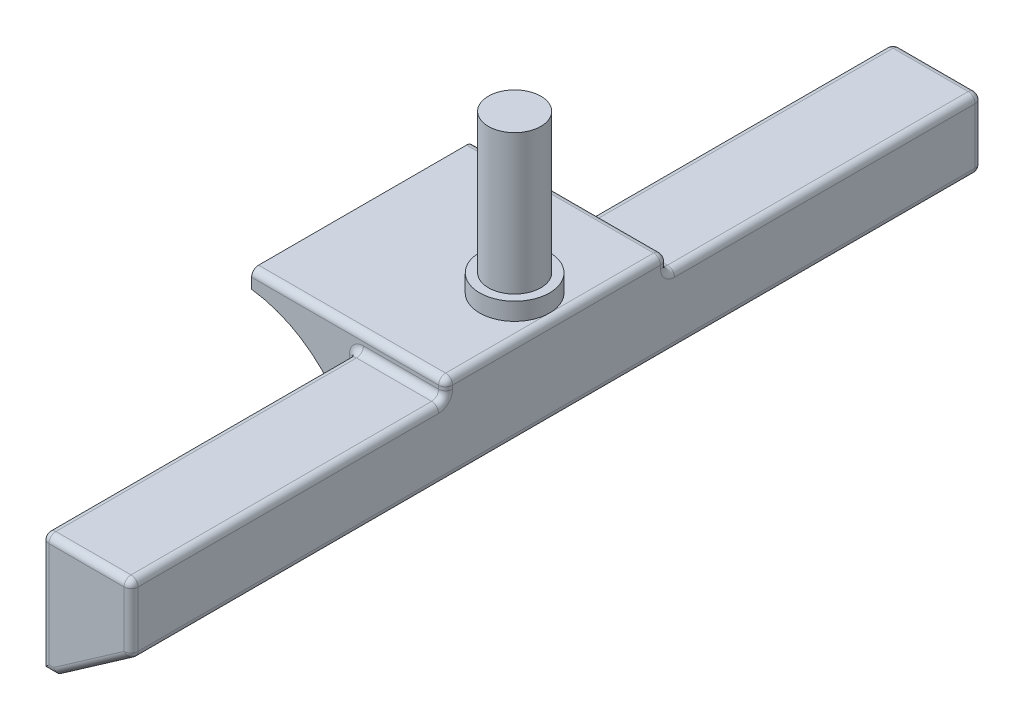
SolidWorks part; units mm, degrees
ref_plane "Front Plane" through (0, 0, 0) normal (0, 0, 1) x (1, 0, 0)
ref_plane "Top Plane" through (0, 0, 0) normal (0, 1, 0) x (1, 0, 0)
ref_plane "Right Plane" through (0, 0, 0) normal (1, 0, 0) x (0, 0, -1)
sketch "Sketch1" plane through (0, 0, 0) normal (0, 1, 0) x (1, 0, 0)
  line L0 (-4, 4) -> (-4, -239.5)
  line L1 (0, 0) -> (17.5, 0)
  line L2 (0, 0) -> (0, -235.5)
  line L3 (0, -235.5) -> (17.5, -235.5)
  line L4 (17.5, 0) -> (17.5, -235.5)
  line L5 (-4, -239.5) -> (21.5, -239.5)
  line L6 (21.5, 4) -> (21.5, -239.5)
  line L7 (-4, 4) -> (21.5, 4)
  dimension "D1" = 17.5
  dimension "D2" = 235.5
  dimension "D3" = 4
extrude "motor -panel connector " add sketch "Sketch1" along normal blind 34
sketch "Sketch3" plane through (0, 34, 0) normal (0, 1, 0) x (1, 0, 0)
  line L1 (-4, 4) -> (21.5, 4)
  line L2 (-4, 4) -> (-4, -239.5)
  line L3 (-4, -239.5) -> (21.5, -239.5)
  line L4 (21.5, 4) -> (21.5, -239.5)
extrude "motor-panel connecctor base" add sketch "Sketch3" against normal blind 4
sketch "Sketch4" plane through (0, 0, 239.5) normal (0, 0, 1) x (1, 0, 0)
  line L0 (0, 0) -> (21.5, 15)
  line L1 (21.5, 34) -> (21.5, 0) construction
  line L2 (21.5, 15) -> (21.5, 0)
  line L3 (21.5, 0) -> (0, 0)
  dimension "D1" = 19
extrude "up down connect cut" cut sketch "Sketch4" against normal blind 250
sketch "Sketch5" plane through (-4, 0, 0) normal (-1, 0, 0) x (0, 0, 1)
  line L0 (-4, 0) -> (239.5, 0) construction
  line L1 (94, 31) -> (141.5, 31)
  line L2 (94, 31) -> (94, 0)
  line L3 (94, 0) -> (141.5, 0)
  line L4 (141.5, 31) -> (141.5, 0)
  line L5 (239.5, 34) -> (239.5, 0) construction
  line L6 (-4, 34) -> (-4, 0) construction
  dimension "D1" = 98
  dimension "D2" = 98
  dimension "D3" = 31
extrude "cut to nail part" cut sketch "Sketch5" against normal blind 5
sketch "Sketch6" plane through (0, 34, 0) normal (0, 1, 0) x (1, 0, 0)
  line L0 (21.5, -239.5) -> (21.5, 4) construction
  line L1 (21.5, -86) -> (-34, -86)
  line L2 (21.5, -86) -> (21.5, -149.5)
  line L3 (21.5, -149.5) -> (-34, -149.5)
  line L4 (-34, -86) -> (-34, -149.5)
  line L5 (-4, 4) -> (-4, -239.5) construction
  line L6 (-4, -239.5) -> (21.5, -239.5) construction
  line L7 (21.5, 4) -> (-4, 4) construction
  point P8 (-34, -117.75)
  dimension "D1" = 30
  dimension "D2" = 90
  dimension "D3" = 90
extrude "panel connector" add sketch "Sketch6" along normal blind 5
sketch "Sketch7" plane through (0, 39, 0) normal (0, 1, 0) x (1, 0, 0)
  line L0 (21.5, -149.5) -> (21.5, -86) construction
  line L1 (21.5, 4) -> (-4, 4) construction
  circle A0 centre (9.5, -117.75) radius 10
  dimension "D1" = 20
  dimension "D2" = 12
  dimension "D3" = 121.75
extrude "Boss-Extrude4" add sketch "Sketch7" along normal blind 5
sketch "Sketch8" plane through (0, 0, 149.5) normal (0, 0, 1) x (1, 0, 0)
  line L0 (-34, 34) -> (-4, 34)
  line L1 (-4, 34) -> (-4, 0)
  arc A0 (-4, 0) -> (-34, 34) centre (-38.2667, 0) ccw
extrude "Boss-Extrude5" add sketch "Sketch8" against normal blind 5
sketch "Sketch13" plane through (0, 0, 86) normal (0, 0, -1) x (-1, 0, 0)
  line L1 (4, 0) -> (4, 34)
  line L2 (4, 34) -> (34, 34)
  arc A0 (34, 34) -> (4, 0) centre (39.8204, -1.3709) ccw
extrude "Boss-Extrude6" add sketch "Sketch13" against normal blind 5
sketch "Sketch14" plane through (0, 44, 0) normal (0, 1, 0) x (1, 0, 0)
  circle A0 centre (9.5, -117.75) radius 7.5
  dimension "D1" = 15
extrude "Boss-Extrude7" add sketch "Sketch14" along normal blind 40
fillet "Fillet3" radius 2 24 edges at (21.5, 39, 117.75) (-6.25, 39, 86) (-6.25, 39, 149.5) (-4, 17, 149.5) (8.75, 34, 239.5) (-4, 17, 86) (21.5, 34, 194.5) (8.75, 34, -4) (21.5, 15, 117.75) (-2, 0, 239.5) (-2, 0, -4) (10.75, 7.5, -4) (10.75, 7.5, 239.5) (21.5, 24.5, -4) (21.5, 24.5, 239.5) (-4, 17, 239.5) (-4, 17, -4) (-4, 34, 41) (-4, 34, 194.5) (21.5, 34, 41) (8.75, 34, 149.5) (21.5, 36.5, 149.5) (8.75, 34, 86) (21.5, 36.5, 86)
